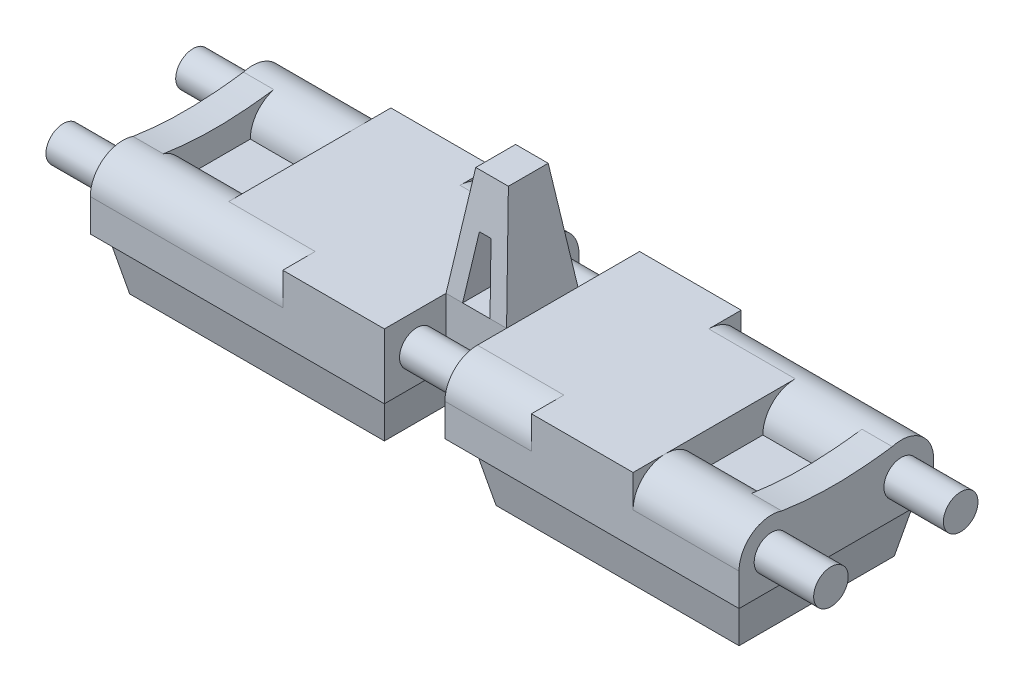
SolidWorks part; units mm, degrees
material "AISI 4340 Aço, normalizado"
ref_plane "Plano frontal" through (0, 0, 0) normal (0, 0, 1) x (1, 0, 0)
ref_plane "Plano superior" through (0, 0, 0) normal (0, 1, 0) x (1, 0, 0)
ref_plane "Plano direito" through (0, 0, 0) normal (1, 0, 0) x (0, 0, -1)
sketch "Esboço1" plane through (0, 0, 0) normal (0, 1, 0) x (1, 0, 0)
  line L1 (7.5, 2.25) -> (-7.5, 2.25)
  line L2 (7.5, 2.25) -> (7.5, -2.25)
  line L3 (7.5, -2.25) -> (-7.5, -2.25)
  line L4 (-7.5, 2.25) -> (-7.5, -2.25)
  line L5 (7.5, 2.25) -> (-7.5, -2.25) construction
  line L6 (7.5, -2.25) -> (-7.5, 2.25) construction
  line L8 (7.5, 7.28) -> (-7.5, 7.28)
  line L9 (-7.5, 7.28) -> (-7.5, 2.78)
  line L10 (7.5, 2.78) -> (-7.5, 2.78)
  line L11 (7.5, 7.28) -> (7.5, 2.78)
  line L12 (7.5, 12.31) -> (-7.5, 12.31)
  line L13 (-7.5, 12.31) -> (-7.5, 7.81)
  line L14 (7.5, 7.81) -> (-7.5, 7.81)
  line L15 (7.5, 12.31) -> (7.5, 7.81)
  line L16 (7.5, 17.34) -> (-7.5, 17.34)
  line L17 (-7.5, 17.34) -> (-7.5, 12.84)
  line L18 (7.5, 12.84) -> (-7.5, 12.84)
  line L19 (7.5, 17.34) -> (7.5, 12.84)
  line L20 (7.5, 22.37) -> (-7.5, 22.37)
  line L21 (-7.5, 22.37) -> (-7.5, 17.87)
  line L22 (7.5, 17.87) -> (-7.5, 17.87)
  line L23 (7.5, 22.37) -> (7.5, 17.87)
  line L24 (7.5, 27.4) -> (-7.5, 27.4)
  line L25 (-7.5, 27.4) -> (-7.5, 22.9)
  line L26 (7.5, 22.9) -> (-7.5, 22.9)
  line L27 (7.5, 27.4) -> (7.5, 22.9)
  line L28 (7.5, 32.43) -> (-7.5, 32.43)
  line L29 (-7.5, 32.43) -> (-7.5, 27.93)
  line L30 (7.5, 27.93) -> (-7.5, 27.93)
  line L31 (7.5, 32.43) -> (7.5, 27.93)
  line L32 (7.5, 37.46) -> (-7.5, 37.46)
  line L33 (-7.5, 37.46) -> (-7.5, 32.96)
  line L34 (7.5, 32.96) -> (-7.5, 32.96)
  line L35 (7.5, 37.46) -> (7.5, 32.96)
  line L36 (7.5, 42.49) -> (-7.5, 42.49)
  line L37 (-7.5, 42.49) -> (-7.5, 37.99)
  line L38 (7.5, 37.99) -> (-7.5, 37.99)
  line L39 (7.5, 42.49) -> (7.5, 37.99)
  line L40 (7.5, 47.52) -> (-7.5, 47.52)
  line L41 (-7.5, 47.52) -> (-7.5, 43.02)
  line L42 (7.5, 43.02) -> (-7.5, 43.02)
  line L43 (7.5, 47.52) -> (7.5, 43.02)
  line L44 (7.5, 52.55) -> (-7.5, 52.55)
  line L45 (-7.5, 52.55) -> (-7.5, 48.05)
  line L46 (7.5, 48.05) -> (-7.5, 48.05)
  line L47 (7.5, 52.55) -> (7.5, 48.05)
  line L48 (7.5, 57.58) -> (-7.5, 57.58)
  line L49 (-7.5, 57.58) -> (-7.5, 53.08)
  line L50 (7.5, 53.08) -> (-7.5, 53.08)
  line L51 (7.5, 57.58) -> (7.5, 53.08)
  line L52 (7.5, 62.61) -> (-7.5, 62.61)
  line L53 (-7.5, 62.61) -> (-7.5, 58.11)
  line L54 (7.5, 58.11) -> (-7.5, 58.11)
  line L55 (7.5, 62.61) -> (7.5, 58.11)
  line L56 (7.5, 67.64) -> (-7.5, 67.64)
  line L57 (-7.5, 67.64) -> (-7.5, 63.14)
  line L58 (7.5, 63.14) -> (-7.5, 63.14)
  line L59 (7.5, 67.64) -> (7.5, 63.14)
  line L60 (7.5, 72.67) -> (-7.5, 72.67)
  line L61 (-7.5, 72.67) -> (-7.5, 68.17)
  line L62 (7.5, 68.17) -> (-7.5, 68.17)
  line L63 (7.5, 72.67) -> (7.5, 68.17)
  line L64 (7.5, 77.7) -> (-7.5, 77.7)
  line L65 (-7.5, 77.7) -> (-7.5, 73.2)
  line L66 (7.5, 73.2) -> (-7.5, 73.2)
  line L67 (7.5, 77.7) -> (7.5, 73.2)
  point P0 (0, 0)
  dimension "D1" = 15
  dimension "D2" = 4.5
  dimension "D4" = 16
sketch "Esboço2" plane through (0, 0, 0) normal (1, 0, 0) x (0, 0, -1)
  line L1 (2.25, 0) -> (-2.25, 0) construction
  line L2 (-2.25, 0) -> (2.25, 0) construction
  circle A0 centre (-1.5, 0) radius 0.75
  circle A1 centre (1.5, 0) radius 0.75
  dimension "D2" = 1.5
  dimension "D3" = 1.5
  dimension "D4" = 1.5
  dimension "D5" = 1.5
extrude "Ressalto-extrusão1" add sketch "Esboço2" along normal mid plane 15
sketch "Esboço3" plane through (7.5, 0, 0) normal (1, 0, 0) x (0, 0, -1)
  arc A0 (-1.2607, 0.7108) -> (-1.2607, -0.7108) centre (-1.5, 0) ccw
  arc A1 (1.2927, -0.7208) -> (1.2927, 0.7208) centre (1.5, 0) ccw
  spline S0 degree 3 poles (-1.2607, 0.7108) (-0.4148, 0.5829) (0.3184, 0.5897) (1.2927, 0.7208) knots 0.079996 0.079996 0.079996 0.079996 0.940072 0.940072 0.940072 0.940072
  spline S1 degree 3 poles (-1.2607, -0.7108) (-0.4148, -0.5829) (0.3184, -0.5897) (1.2927, -0.7208) knots 0.079996 0.079996 0.079996 0.079996 0.940072 0.940072 0.940072 0.940072
extrude "Ressalto-extrusão2" add sketch "Esboço3" against normal blind 0.7 contours S0 A1 S1 A0
sketch "Esboço4" plane through (-7.5, 0, 0) normal (-1, 0, 0) x (0, 0, 1)
  arc A2 (1.2607, -0.7108) -> (1.2607, 0.7108) centre (1.5, 0) ccw
  arc A3 (-1.2927, 0.7208) -> (-1.2927, -0.7208) centre (-1.5, 0) ccw
  arc A4 (1.2607, -0.7108) -> (1.2607, 0.7108) centre (1.5, 0) ccw
  arc A5 (-1.2927, 0.7208) -> (-1.2927, -0.7208) centre (-1.5, 0) ccw
  spline S2 degree 3 poles (-2999.8973, -74.8249) (2931.6638, -30.9793) (-2927.309, 137.5156) (2990.4013, -249.8059) knots -16.773603 -16.773603 -16.773603 -16.773603 18.085144 18.085144 18.085144 18.085144 only from (-1.2927, -0.7208) to (1.2607, -0.7108)
  spline S3 degree 3 poles (2990.4519, 249.8092) (-2927.3195, -137.515) (2931.6353, 30.9779) (-2999.8283, 74.8244) knots -17.065175 -17.065175 -17.065175 -17.065175 17.793537 17.793537 17.793537 17.793537 only from (1.2607, 0.7108) to (-1.2927, 0.7208)
  spline S4 degree 3 poles (-1.2927, -0.7208) (-0.3184, -0.5897) (0.4148, -0.5829) (1.2607, -0.7108) knots 0.079996 0.079996 0.079996 0.079996 0.940072 0.940072 0.940072 0.940072
  spline S5 degree 3 poles (1.2607, 0.7108) (0.4148, 0.5829) (-0.3184, 0.5897) (-1.2927, 0.7208) knots 0.079996 0.079996 0.079996 0.079996 0.940072 0.940072 0.940072 0.940072
  dimension "D1" = 0
extrude "Ressalto-extrusão3" add sketch "Esboço4" against normal blind 0.7
sketch "Esboço5" plane through (0, 0, 0) normal (0, 1, 0) x (1, 0, 0)
  line L1 (5.05, 2.25) -> (-5.05, 2.25)
  line L2 (5.05, 2.25) -> (5.05, -2.25)
  line L3 (5.05, -2.25) -> (-5.05, -2.25)
  line L4 (-5.05, 2.25) -> (-5.05, -2.25)
  line L5 (5.05, 2.25) -> (-5.05, -2.25) construction
  line L6 (5.05, -2.25) -> (-5.05, 2.25) construction
  point P0 (0, 0)
  dimension "D1" = 10.1
  dimension "D2" = 4.5
extrude "Ressalto-extrusão4" add sketch "Esboço5" along normal blind 0.75 and the other way blind 0.75
sketch "Esboço6" plane through (0, 0.75, 0) normal (0, 1, 0) x (1, 0, 0)
  line L0 (-0.7, 0.825) -> (-0.7, 2.6051)
  line L1 (0.7, 0.825) -> (-0.7, 0.825)
  line L3 (0.7, -0.825) -> (-0.7, -0.825)
  line L5 (0.7, 0.825) -> (-0.7, -0.825) construction
  line L6 (0.7, -0.825) -> (-0.7, 0.825) construction
  line L7 (-0.7, 2.6051) -> (0.7, 2.6051)
  line L8 (0.7, 2.6051) -> (0.7, 0.825)
  line L9 (0.7, 0.825) -> (0.6726, 0.8274)
  line L10 (-0.7, -0.825) -> (-0.7, -2.5167)
  line L11 (-0.7, -2.5167) -> (0.7, -2.5167)
  line L12 (0.7, -2.5167) -> (0.7, -0.825)
  point P0 (0, 0)
  line M6 (5.05, 2.25) -> (-5.05, 2.25)
  line M10 (-5.05, -2.25) -> (5.05, -2.25)
  dimension "D1" = 1.65
  dimension "D2" = 1.4
extrude "Corte-extrusão1" cut sketch "Esboço6" against normal blind 10.75 contours L12 L3 L10 M10 | L8 L0 L1 M6 region at (0, 0.75, -1.5375) region at (0, 0.75, 1.5375)
sketch "Esboço10" plane through (5.05, 0, 0) normal (1, 0, 0) x (0, 0, -1)
  line L2 (2.25, 0) -> (2.25, 0.75)
  line L3 (2.25, 0) -> (2.25, 0.75)
  line L5 (2.25, 0.75) -> (1.5, 0.75)
  line L8 (2.25, 0.75) -> (1.5, 0.75)
  arc A1 (2.25, 0) -> (1.5, 0.75) centre (1.5, 0) ccw
  arc A2 (2.25, 0) -> (1.5, 0.75) centre (1.5, 0) ccw
  dimension "D1" = 0
extrude "Corte-extrusão4" cut sketch "Esboço10" against normal blind 2
sketch "Esboço11" plane through (-0.7, 0, 0) normal (1, 0, 0) x (0, 0, -1)
  line L2 (2.25, 0) -> (2.25, 0.75)
  line L3 (2.25, 0) -> (2.25, 0.75)
  line L5 (2.25, 0.75) -> (1.5, 0.75)
  line L8 (2.25, 0.75) -> (1.5, 0.75)
  arc A1 (2.25, 0) -> (1.5, 0.75) centre (1.5, 0) ccw
  arc A2 (2.25, 0) -> (1.5, 0.75) centre (1.5, 0) ccw
  dimension "D1" = 0
extrude "Corte-extrusão5" cut sketch "Esboço11" against normal blind 2
sketch "Esboço12" plane through (-5.05, 0, 0) normal (-1, 0, 0) x (0, 0, 1)
  line L2 (2.25, 0) -> (2.25, 0.75)
  line L3 (2.25, 0.75) -> (1.5, 0.75)
  line L4 (2.25, 0) -> (2.25, 0.75)
  line L5 (2.25, 0.75) -> (1.5, 0.75)
  arc A1 (2.25, 0) -> (1.5, 0.75) centre (1.5, 0) ccw
  arc A2 (2.25, 0) -> (1.5, 0.75) centre (1.5, 0) ccw
  dimension "D1" = 0
extrude "Corte-extrusão6" cut sketch "Esboço12" against normal blind 2
sketch "Esboço13" plane through (0.7, 0, 0) normal (-1, 0, 0) x (0, 0, 1)
  line L2 (2.25, 0) -> (2.25, 0.75)
  line L3 (2.25, 0.75) -> (1.5, 0.75)
  line L4 (2.25, 0) -> (2.25, 0.75)
  line L5 (2.25, 0.75) -> (1.5, 0.75)
  arc A1 (2.25, 0) -> (1.5, 0.75) centre (1.5, 0) ccw
  arc A2 (2.25, 0) -> (1.5, 0.75) centre (1.5, 0) ccw
  dimension "D1" = 0
extrude "Corte-extrusão7" cut sketch "Esboço13" against normal blind 2
sketch "Esboço14" plane through (0, -0.75, 0) normal (0, -1, 0) x (1, 0, 0)
  line L1 (-0.9, 2.05) -> (-7.3, 2.05)
  line L2 (-0.9, 2.05) -> (-0.9, -2.05)
  line L3 (-0.9, -2.05) -> (-7.3, -2.05)
  line L4 (-7.3, 2.05) -> (-7.3, -2.05)
  line L5 (-0.9, 2.05) -> (-7.3, -2.05) construction
  line L6 (-0.9, -2.05) -> (-7.3, 2.05) construction
  line L7 (-0.7, 2.25) -> (-0.7, 0.825) construction
  line L8 (7.5, 2.25) -> (-7.5, 2.25) construction
  line L9 (7.5, -2.25) -> (-7.5, -2.25) construction
  line L10 (-7.5, 2.25) -> (-7.5, 1.2607) construction
  line L11 (1.1725, -2.05) -> (7.3, 2.05) construction
  line L12 (1.1725, 2.05) -> (7.3, -2.05) construction
  line L13 (7.3, 2.05) -> (7.3, -2.05)
  line L14 (1.1725, -2.05) -> (7.3, -2.05)
  line L15 (1.1725, 2.05) -> (1.1725, -2.05)
  line L16 (1.1725, 2.05) -> (7.3, 2.05)
  line L17 (7.5, 1.2607) -> (7.5, 2.25) construction
  point P0 (-4.1, 0)
  point P20 (2.875, 0)
  dimension "D1" = 0.2
  dimension "D2" = 0.2
  dimension "D3" = 0.2
  dimension "D4" = 0.2
  dimension "D5" = 0.2
sketch "Esboço15" plane through (0, 0, 0.825) normal (0, 0, 1) x (1, 0, 0)
  line L0 (-0.7, 0.75) -> (-0.377, 3.25)
  line L1 (-0.7, 0.75) -> (-0.3168, 0.75)
  line L3 (-0.3168, 0.75) -> (-0.1343, 2.1633)
  line L5 (-0.377, 3.25) -> (0.377, 3.25)
  line L6 (0.7, 0.75) -> (0.377, 3.25)
  line L7 (0.3168, 0.75) -> (0.7, 0.75)
  line L8 (0.3168, 0.75) -> (0.1343, 2.1633)
  line L9 (-0.1343, 2.1633) -> (0.1343, 2.1633)
  line L11 (-0.3231, 0.7013) -> (-0.0429, 2.87) construction
  line L13 (0.3231, 0.7013) -> (0.0429, 2.87) construction
  line L14 (-0.0429, 2.87) -> (0.0429, 2.87) construction
  dimension "D1" = 0.38
extrude "Ressalto-extrusão6" add sketch "Esboço15" against normal up to surface (1.65 mm away) up to face at (0, 0, -0.825)
sketch "Esboço16" plane through (5.05, 0, 0) normal (1, 0, 0) x (0, 0, -1)
  line L0 (-0.4605, 3.25) -> (0.4605, 3.25)
  line L1 (0.825, 3.25) -> (-0.825, 3.25) construction
  line L3 (-0.4605, 3.25) -> (-0.825, 0.75)
  line L4 (-0.825, 0.75) -> (-1.6415, 3.918)
  line L5 (-1.6415, 3.918) -> (1.7008, 3.6886)
  line L6 (1.7008, 3.6886) -> (0.825, 0.75)
  line L7 (0.825, 0.75) -> (0.4605, 3.25)
extrude "Corte-extrusão8" cut sketch "Esboço16" against normal blind 8.2
sketch "Esboço17" plane through (0, 0, 0) normal (1, 0, 0) x (0, 0, -1)
  circle A0 centre (-1.5, 0) radius 0.4
  circle A1 centre (1.5, 0) radius 0.4
  dimension "D1" = 0.8
  dimension "D2" = 0.8
extrude "Ressalto-extrusão7" add sketch "Esboço17" along normal mid plane 17.75
sketch "Esboço18" plane through (0, 0, 0) normal (0, 1, 0) x (1, 0, 0)
  line L0 (7.5, 2.25) -> (5.05, 2.25)
  line L1 (5.05, 2.25) -> (5.05, -2.25)
  line L2 (5.05, -2.25) -> (7.5, -2.25)
  line L3 (7.5, -2.25) -> (7.5, 2.25)
  line L4 (-7.5, 2.25) -> (-5.05, 2.25)
  line L5 (-5.05, 2.25) -> (-5.05, -2.25)
  line L6 (-5.05, -2.25) -> (-7.5, -2.25)
  line L7 (-7.5, -2.25) -> (-7.5, 2.25)
extrude "Ressalto-extrusão8" add sketch "Esboço18" against normal up to surface (0.75 mm away) up to face at (0, -0.75, 0)
extrude "Ressalto-extrusão9" add sketch "Esboço14" along normal blind 1.2 draft 12 separate body contours L16 L13 L14 L15 | L1 L4 L3 L2
sketch "Esboço19" plane through (0, 0, 0) normal (1, 0, 0) x (0, 0, -1)
  point P0 (-1.5, 0)
  point P1 (1.5, 0)
